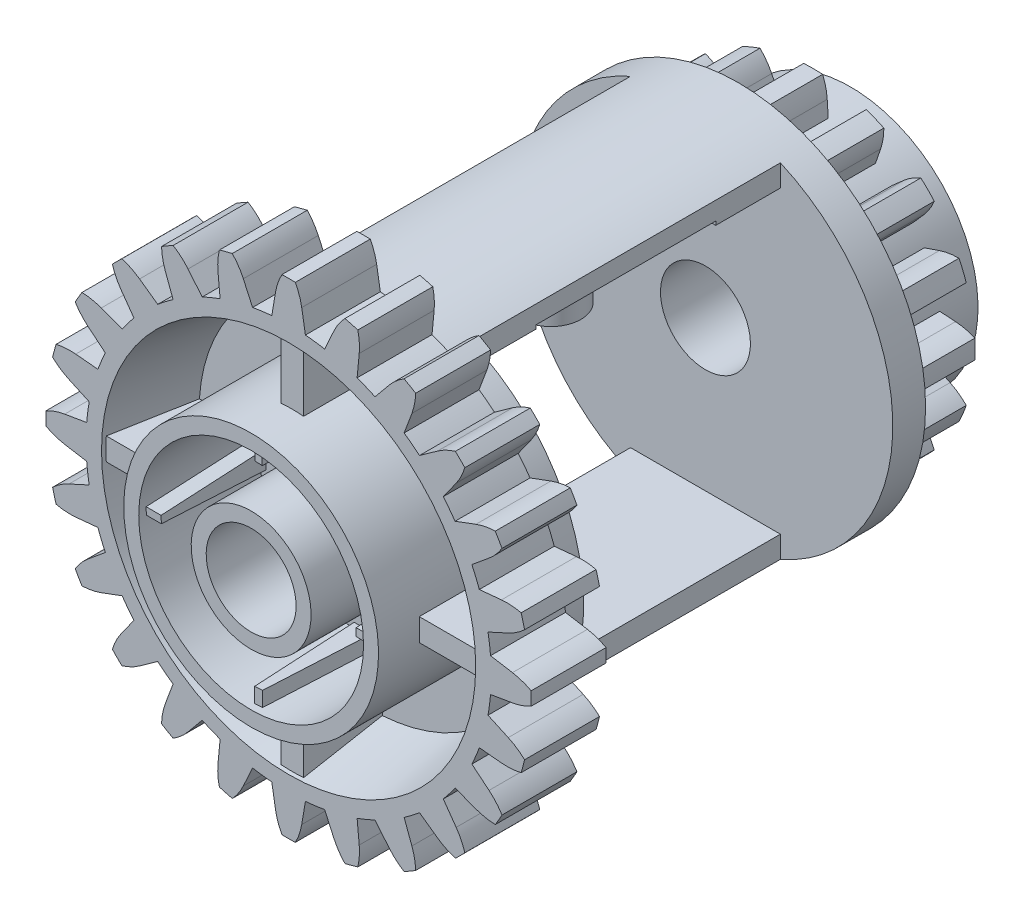
SolidWorks part; units mm, degrees
material "ABS"
ref_plane "Front Plane" through (0, 0, 0) normal (0, 0, 1) x (1, 0, 0)
ref_plane "Top Plane" through (0, 0, 0) normal (0, 1, 0) x (1, 0, 0)
ref_plane "Right Plane" through (0, 0, 0) normal (1, 0, 0) x (0, 0, -1)
sketch "Sketch2" plane through (0, 0, 0) normal (1, 0, 0) x (0, 0, -1)
  line L3 (16, 6) -> (9.9998, 6)
  line L4 (-9.6, 6) -> (-16, 6)
  line L5 (5.0474, 0) -> (-5.0474, 0) construction
  line L6 (-10, 10) -> (-10, 12.95)
  line L8 (-10, 12.95) -> (-14, 12.95)
  line L10 (-16, 6.8) -> (-9.6, 6.8)
  line L11 (-9.6, 6.8) -> (-9.6, 9.1812)
  line L12 (-9.6, 9.1812) -> (-14, 9.9863)
  line L13 (9.9997, 8.65) -> (13.9997, 8.65)
  line L14 (13.9997, 8.65) -> (13.9997, 6.8)
  line L15 (9.9997, 8.65) -> (9.9996, 10)
  line L231 (9.9996, 10) -> (-10, 10)
  line L245 (16, 6.8) -> (13.9997, 6.8)
  line L249 (16, 6) -> (16, 6.8)
  line L259 (9.9999, 3.2) -> (9.9998, 6)
  line L261 (16, 3.2) -> (9.9999, 3.2)
  line L265 (16, 2.4) -> (16, 3.2)
  line L267 (8.25, 2.4) -> (16, 2.4)
  line L270 (8.25, 8) -> (8.25, 2.4)
  line L271 (-8.25, 8) -> (8.25, 8)
  line L295 (-8.25, 2.4) -> (-8.25, 8)
  line L298 (-16, 2.4) -> (-8.25, 2.4)
  line L300 (-16, 3.2) -> (-16, 2.4)
  line L304 (-9.6, 3.2) -> (-16, 3.2)
  line L306 (-9.6, 6) -> (-9.6, 3.2)
  line L316 (-16, 6.8) -> (-16, 6)
  line L323 (-14, 12.95) -> (-14, 9.9863)
  point P10 (0, 0)
  dimension "D2" = 0.8
  dimension "D3" = 10
  dimension "D4" = 12.95
  dimension "D5" = 0.8
  dimension "D6" = 8.65
  dimension "D7" = 4
  dimension "D1" = 14
  dimension "D8" = 4
  dimension "D9" = 8
  dimension "D10" = 8.25
  dimension "D11" = 8.25
  dimension "D12" = 9.6
  dimension "D13" = 10
  dimension "D14" = 16
  dimension "D15" = 16
  dimension "D16" = 6.8
  dimension "D17" = 2.4
revolve "Revolve1" add sketch "Sketch2" angle 180 about L5 reverse direction yes
sketch "Sketch3" plane through (0, 0, 0) normal (0, 1, 0) x (1, 0, 0)
  line L0 (0, 9.9996) -> (0, -10) construction
  line L1 (4, -8.25) -> (4, 8.25)
  line L2 (4, 8.25) -> (10, 8.25)
  line L3 (10, 8.25) -> (10, -8.25)
  line L4 (10, -8.25) -> (4, -8.25)
  line L5 (0, 8.25) -> (8, 8.25) construction
  line L6 (8, -8.25) -> (0, -8.25) construction
  line L7 (10, -10) -> (10, 9.9996) construction
  dimension "D1" = 4
extrude "Cut-Extrude2" cut sketch "Sketch3" against normal through all both and the other way through all
sketch "Sketch5" plane through (0, 0, 0) normal (1, 0, 0) x (0, 0, -1)
  line L0 (-8.25, 8) -> (8.25, 8) construction
  line L1 (-8.25, 8) -> (8.25, 8)
  line L2 (8.25, 8) -> (8.25, 2.4) construction
  line L3 (8.25, 8) -> (8.25, -8)
  line L4 (-8.25, 2.4) -> (-8.25, 8) construction
  line L5 (-8.25, -8) -> (-8.25, 8)
  line L6 (-8.25, -8) -> (8.25, -8) construction
  line L7 (-8.25, -8) -> (8.25, -8)
  line L8 (4.8, 8) -> (4.8, 8.2)
  line L9 (4.8, 8.2) -> (-4.8, 8.2)
  line L10 (-4.8, 8.2) -> (-4.8, 8)
  point P9 (0, 8.2)
  dimension "D1" = 9.6
  dimension "D2" = 0.2
extrude "Cut-Extrude3" cut sketch "Sketch5" along normal through all contours L7 | L5 L7 L3 L1 | L9 L10 L1 L8 region at (0, 0, 0) region at (0, 8.1, 0)
mirror "Mirror1" about plane through (0, 0, 0) normal (1, 0, 0) of bodies 105
sketch "Sketch7" plane through (0, 0, 14) normal (0, 0, 1) x (1, 0, 0)
  line L3 (0.8968, 10.7778) -> (0.7, 11.95)
  line L5 (2.4167, 11.724) -> (1.9232, 10.6426)
  line L6 (0.8968, 10.7778) -> (1.9232, 10.6426) construction
  circle A0 centre (0, 0) radius 12.95 construction
  arc A1 (3.0052, 12.5965) -> (0.3575, 12.9451) centre (0, 0) ccw
  arc A2 (1.9232, 10.6426) -> (0.8968, 10.7778) centre (0, 0) ccw
  arc A3 (0.7, 11.95) -> (0.3575, 12.9451) centre (-2.4558, 11.4201) ccw
  arc A4 (2.4167, 11.724) -> (3.0052, 12.5965) centre (5.3279, 10.3954) cw
  dimension "D1" = 3.2
  dimension "D2" = 3.2
extrude "Cut-Extrude5" cut sketch "Sketch7" against normal up to surface (4 mm away) up to face at (0, -12.95, 10)
pattern_circular "CirPattern1" count 24 over 360 about axis through (0, 0, -5.0474) along (0, 0, 1) of "Cut-Extrude5"
sketch "Sketch8" plane through (0, 0, -13.9997) normal (0, 0, -1) x (-1, 0, 0)
  line L1 (-0.75, 7.6) -> (-0.8039, 6.7523)
  line L3 (-2.2155, 7.3085) -> (-1.8413, 6.546)
  circle A0 centre (0, 0) radius 6.8 construction
  arc A1 (-0.8039, 6.7523) -> (-1.8413, 6.546) centre (0, 0) ccw
  circle A2 centre (0, 0) radius 8.65 construction
  arc A3 (-0.5072, 8.6351) -> (-2.8359, 8.1719) centre (0, 0) ccw
  arc A4 (-2.2155, 7.3085) -> (-2.8359, 8.1719) centre (-5.0882, 5.8987) ccw
  arc A5 (-0.75, 7.6) -> (-0.5072, 8.6351) centre (2.4435, 7.3969) cw
  dimension "D1" = 3.2
  dimension "D2" = 3.2
extrude "Cut-Extrude6" cut sketch "Sketch8" against normal up to surface (3.9999 mm away) up to face at (0, -10, -9.9996)
pattern_circular "CirPattern2" count 16 over 360 about axis through (0, 0, -5.0474) along (0, 0, 1) of "Cut-Extrude6"
sketch "Sketch9" plane through (0, 8, 0) normal (0, -1, 0) x (1, 0, 0)
  circle A0 centre (0, 0) radius 1.6
  dimension "D1" = 3.2
extrude "Boss-Extrude1" add sketch "Sketch9" along normal blind 3.15 and the other way up to next
sketch "Sketch10" plane through (0, 0, 9.6) normal (0, 0, 1) x (1, 0, 0)
  line L1 (9.9683, 0.6) -> (6.7734, 0.6008)
  line L3 (9.9683, -0.6) -> (6.7734, -0.6008)
  circle A0 centre (0, 0) radius 9.9863 construction
  arc A1 (9.9683, -0.6) -> (9.9683, 0.6) centre (0, 0) ccw
  circle A2 centre (0, 0) radius 6.8 construction
  arc A3 (6.7734, -0.6008) -> (6.7734, 0.6008) centre (0, 0) ccw
  circle A4 centre (0, 0) radius 6.8 construction
extrude "Boss-Extrude2" add sketch "Sketch10" along normal offset from surface (4.2 mm away) 0.2 up to face at (0, -9.9863, 14)
ref_plane "Plane1" through (5.2, 0, 0) normal (1, 0, 0) x (0, 0, -1)
sketch "Sketch11" plane through (5.2, 0, 0) normal (1, 0, 0) x (0, 0, -1)
  line L0 (-15.6, 0) -> (15.6, 0) construction
  line L1 (-15.608, -0.1998) -> (-10, -0.5)
  line L3 (-15.608, -0.1998) -> (-15.5919, 0.1998)
  line L4 (-10, -10) -> (-10, 10) construction
  line L5 (-15.5919, 0.1998) -> (-10, 0.5)
  line L7 (-10, -0.5) -> (-10, 0.5)
  line L9 (10, 0.5) -> (15.6, 0.2)
  line L11 (10, -0.5) -> (10, 0.5)
  line L13 (15.6, -0.2) -> (10, -0.5)
  line L15 (15.6, 0.2) -> (15.6, -0.2)
  point P12 (0, 0)
  point P18 (10, 0)
  point P21 (-10, 0)
  point P22 (-15.6, 0)
  dimension "D2" = 1
  dimension "D3" = 0.4
extrude "Boss-Extrude3" add sketch "Sketch11" along normal blind 1.2
pattern_circular "CirPattern3" count 4 over 360 about axis through (0, 0, -5.0474) along (0, 0, 1) of "Boss-Extrude2", "Boss-Extrude3"
equation "\"D2@Sketch8\"=\"D1@Sketch8\""
